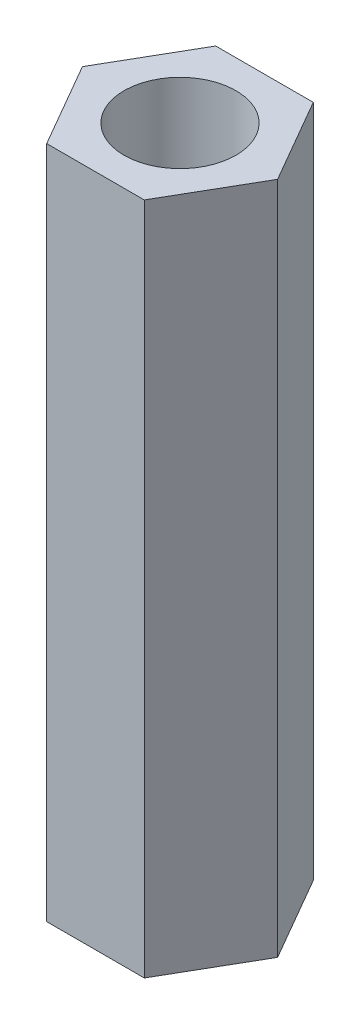
SolidWorks part; units mm, degrees
note: '?' marks a value the reader was unsure of.
ref_plane "Front Plane" through (0, 0, 0) normal (0, 0, 1) x (1, 0, 0)
ref_plane "Top Plane" through (0, 0, 0) normal (0, 1, 0) x (1, 0, 0)
ref_plane "Right Plane" through (0, 0, 0) normal (1, 0, 0) x (0, 0, -1)
sketch "Sketch1" plane through (0, 0, 0) normal (0, 1, 0) x (1, 0, 0)
  circle A0 centre (0, 0) radius 9.398
  dimension "D1" = 18.796
extrude "Boss-Extrude1" add sketch "Sketch1" along normal blind 74.93
sketch "Sketch2" plane through (0, 74.93, 0) normal (0, 1, 0) x (1, 0, 0)
  circle A0 centre (0, 0) radius 6.223
  dimension "D1" = 12.446
extrude "Cut-Extrude1" cut sketch "Sketch2" against normal blind 69.088
ref_axis "Axis1" through (0, 5.842, 0) along (0, 1, 0)?
sketch "Sketch7" plane through (0, 74.93, 0) normal (0, 1, 0) x (1, 0, 0)
  line L1 (10.8519, 0) -> (5.4259, 9.398)
  line L2 (5.4259, 9.398) -> (-5.4259, 9.398)
  line L3 (-5.4259, 9.398) -> (-10.8519, 0)
  line L4 (-10.8519, 0) -> (-5.4259, -9.398)
  line L5 (-5.4259, -9.398) -> (5.4259, -9.398)
  line L6 (5.4259, -9.398) -> (10.8519, 0)
  circle A0 centre (0, 0) radius 9.398 construction
  circle M2 centre (0, 0) radius 9.398
  dimension "D1" = 18.796
extrude "Boss-Extrude2" add sketch "Sketch7" against normal up to surface (74.93 mm away) contours L2 L3 M2 | L1 L2 M2 | L6 L1 M2 | L5 L6 M2 | L4 L5 M2 | L3 L4 M2 up to face at (0, 0, 9.398)
sketch "Sketch8" plane through (0, 0, 0) normal (0, -1, 0) x (1, 0, 0)
  line L0 (-10.8519, 0) -> (-5.4259, -9.398) construction
  line L1 (-1.7598, -5.588) -> (-2.493, -4.318)
  line L2 (-2.493, -4.318) -> (-3.9595, -4.318)
  line L3 (-3.9595, -4.318) -> (-4.6927, -5.588)
  line L4 (-4.6927, -5.588) -> (-3.9595, -6.858)
  line L5 (-3.9595, -6.858) -> (-2.493, -6.858)
  line L6 (-2.493, -6.858) -> (-1.7598, -5.588)
  line L7 (-5.4259, -9.398) -> (5.4259, -9.398) construction
  circle A0 centre (-3.2262, -5.588) radius 1.27 construction
  dimension "D3" = 2.54
  dimension "D1" = 2.54
  dimension "D2" = 2.54
extrude "Cut-Extrude6" cut sketch "Sketch8" against normal blind 4.318
pattern_circular "CirPattern2" count 6 over 360 about axis through (0.06, 0, 0.1039) along (0, 1, 0) of "Cut-Extrude6"
equation "\"chalk_length\"= 2.95in"
equation "\"chalk_diameter\"= 0.47in"
equation "\"drum_diameter\"= 4.25in"
equation "\"drum_thickness\" = 0.2in"
equation "\"drum_height\"= 3.75in"
equation "\"axis_diameter\" = 0.5in"
equation "\"axis_grips\"= \"axis_diameter\" / 4"
equation "\"axis_insert_gap\"= \"axis_diameter\" / 4"
equation "\"tight_fit\" = 0.005in"
equation "\"normal_fit\" = 0.010in"
equation "\"loose_fit\" = 0.020in"
equation "\"chalk_slot_diameter\"= 0.75in"
equation "\"chalk_slot_height\"= 2.95in"
equation "\"chalk_padding_gap\"= 0.10in"
equation "\"D1@Sketch1\"=\"hexagonal_diameter\" - \"normal_fit\""
equation "\"D1@Boss-Extrude1\"=\"chalk_slot_height\""
equation "\"D1@Sketch2\"=\"chalk_diameter\"+\"loose_fit\""
equation "\"D1@Cut-Extrude1\"=\"chalk_length\" + \"loose_fit\" - 0.25in'Subtracting 0.25 for chalk to be grabbable"
equation "\"top_diameter\"= \"drum_diameter\" - 2 * \"drum_thickness\" - \"loose_fit\""
equation "\"top_thickness\"= 0.2in"
equation "\"hexagonal_diameter\"= 0.75in'Can't be less than axis_diaemeter + top_thickness. Hexagonal diameter for top interface and chalk_slot"
equation "\"hexagonal_female_diameter\"= 0.10in'All hexagons use inscribed unless otherwise explicit"
equation "\"hexagonal_female_spacing\"= 0.10in"
equation "\"hexagonal_female_height\"= 0.15in"
equation "\"D1@Sketch7\"=\"hexagonal_diameter\" -\"normal_fit\""
equation "\"D1@Sketch8\"=\"hexagonal_female_spacing\""
equation "\"D2@Sketch8\"=\"hexagonal_female_spacing\""
equation "\"D3@Sketch8\"=\"hexagonal_female_diameter\""
equation "\"D1@Cut-Extrude6\"=\"hexagonal_female_height\" + \"loose_fit\""
equation "\"carousel_height\" = 0.4in"
equation "\"cap_height\" = 0.5in"
equation "\"cap_depth\" = 0.5in"
equation "\"Feature Radius@Sketch6\" = \"hexagonal_diameter\" * 2"
equation "\"D1@Sketch6\"=\"hexagonal_female_spacing\" - 0.5*\"loose_fit\""
equation "\"D1@Sketch5\"=\"axis_grips\""
equation "\"D3@Sketch6\"=\"hexagonal_female_diameter\" + \"loose_fit\""
equation "\"D2@Sketch6\"=\"hexagonal_female_spacing\" - 0.5*\"loose_fit\""
equation "\"D1\" = \"hexagonal_female_height\" + \"loose_fit\""
